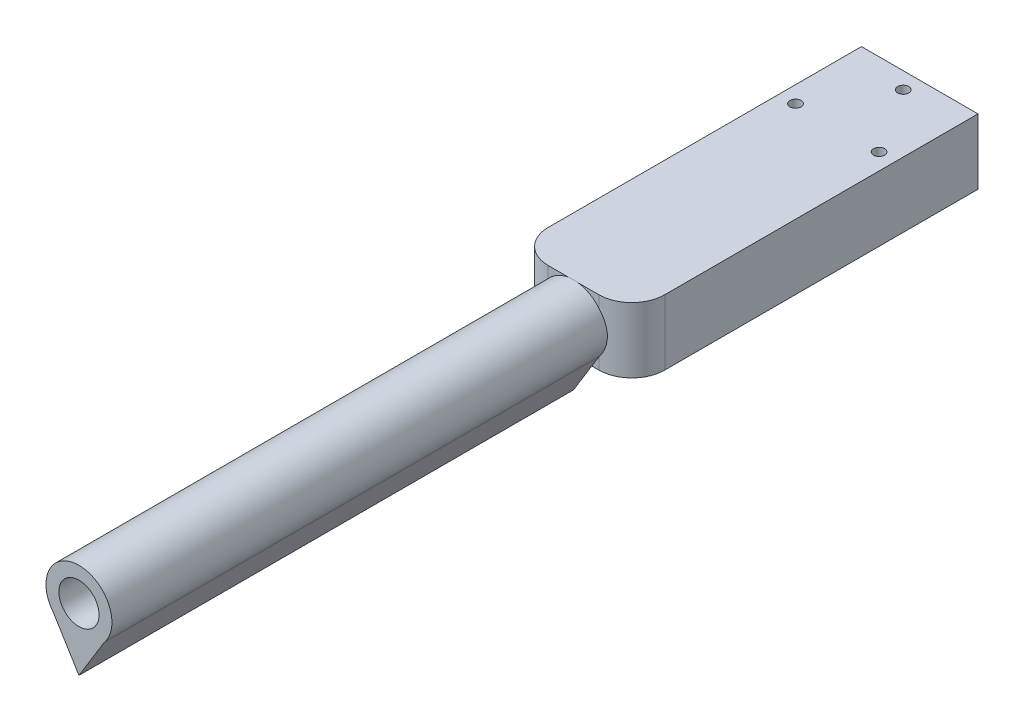
SolidWorks part; units mm, degrees
ref_plane "Ön Düzlem" through (0, 0, 0) normal (0, 0, 1) x (1, 0, 0)
ref_plane "Üst Düzlem" through (0, 0, 0) normal (0, 1, 0) x (1, 0, 0)
ref_plane "Sağ Düzlem" through (0, 0, 0) normal (1, 0, 0) x (0, 0, -1)
sketch "Çizim1" plane through (0, 0, 0) normal (0, 0, 1) x (1, 0, 0)
  line L0 (0, -18.9298) -> (-7.7009, -6.3793)
  line L1 (0, -18.9298) -> (7.7009, -6.3793)
  arc A0 (7.7009, -6.3793) -> (-7.7009, -6.3793) centre (0, 0) ccw
  circle A2 centre (0, 0) radius 6.1
extrude "Yükseklik-Ekstrüzyon1" add sketch "Çizim1" along normal blind 150
sketch "Çizim2" plane through (0, 0, 0) normal (0, 0, 1) x (1, 0, 0)
  line L1 (-17.6734, 9.9005) -> (17.6734, 9.9005)
  line L2 (-17.6734, 9.9005) -> (-17.6734, -9.9005)
  line L3 (-17.6734, -9.9005) -> (17.6734, -9.9005)
  line L4 (17.6734, 9.9005) -> (17.6734, -9.9005)
  line L5 (-17.6734, 9.9005) -> (17.6734, -9.9005) construction
  line L6 (-17.6734, -9.9005) -> (17.6734, 9.9005) construction
  point P0 (0, 0)
extrude "Yükseklik-Ekstrüzyon2" add sketch "Çizim2" against normal blind 105
fillet "Radyus6" radius 10 2 edges at (-17.6734, 0, 0) (17.6734, 0, 0)
sketch "Çizim3" plane through (0, 9.9005, 0) normal (0, 1, 0) x (1, 0, 0)
  line L0 (17.6734, 105) -> (17.6734, 10) construction
  line L1 (-17.6734, 105) -> (17.6734, 105)
  line L2 (-17.6734, 105) -> (-17.6734, 75)
  line L3 (-17.6734, 75) -> (17.6734, 75)
  line L4 (17.6734, 105) -> (17.6734, 75)
  line L5 (0, 105) -> (0, 100)
  line L14 (-17.6748, 80.0029) -> (-12.6748, 80.0029)
  line L15 (-17.6748, 80.0029) -> (-17.6748, 75.0029)
  line L16 (-17.6748, 75.0029) -> (-12.6748, 75.0029)
  line L17 (-12.6748, 80.0029) -> (-12.6748, 75.0029)
  line L18 (17.672, 80.0029) -> (12.6695, 80.0029)
  line L19 (17.672, 80.0029) -> (17.672, 75.0029)
  line L20 (17.672, 75.0029) -> (12.6695, 75.0029)
  line L21 (12.6695, 80.0029) -> (12.6695, 75.0029)
sketch "Çizim13" plane through (0, 0, 0) normal (0, 0, 1) x (1, 0, 0)
  circle A0 centre (0, 0) radius 6.1
extrude "Kes-Ekstrüzyon1" cut sketch "Çizim13" against normal mid plane 300
hole_wizard "M3 Boşluklu Delik1" positions "Çizim14" profile "Çizim15" hole size "M3" standard "ANSI Metrik" end condition through all
sketch "Çizim14" plane through (0, 9.9005, 0) normal (0, 1, 0) x (1, 0, 0)
  point P0 (0, 100)
  point P3 (-12.6748, 80.0029)
  point P6 (12.6695, 80.0029)
sketch "Çizim15" plane through (0, 9.9005, -100) normal (1, 0, 0) x (0, 0, 1)
  line L0 (0, 0) -> (0, 28.8304)
  line L1 (0, 28.8304) -> (1.7, 28.8304)
  line L2 (1.7, 28.8304) -> (1.7, 0)
  line L5 (1.7, 0) -> (0, 0)
  line L11 (0, -6.35) -> (0, 107.95) construction
  dimension "Thru Hole Dia." = 3.4
  dimension "Thru Hole Depth" = 28.8304
